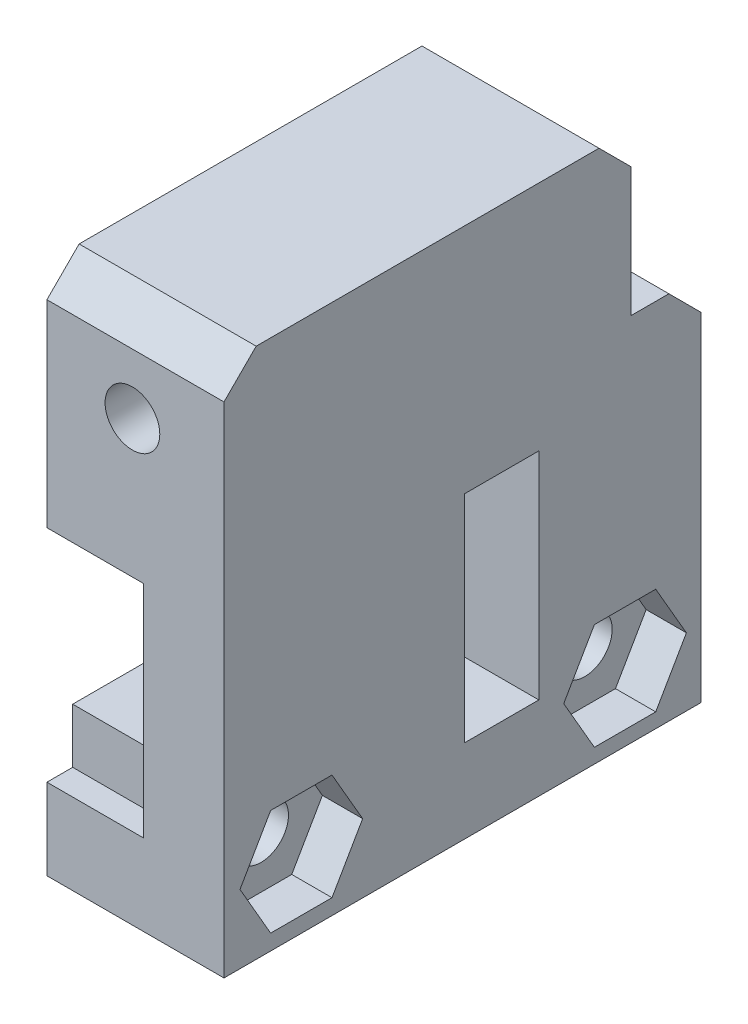
SolidWorks part; units mm, degrees
ref_plane "Front Plane" through (0, 0, 0) normal (0, 0, 1) x (1, 0, 0)
ref_plane "Top Plane" through (0, 0, 0) normal (0, 1, 0) x (1, 0, 0)
ref_plane "Right Plane" through (0, 0, 0) normal (1, 0, 0) x (0, 0, -1)
sketch "Sketch1" plane through (0, 0, 0) normal (1, 0, 0) x (0, 0, -1)
  line L1 (-14.8204, 11.4976) -> (14.8204, 11.4976)
  line L2 (-14.8204, 11.4976) -> (-14.8204, -11.4976)
  line L3 (-14.8204, -11.4976) -> (14.8204, -11.4976)
  line L4 (14.8204, 11.4976) -> (14.8204, -11.4976)
  line L5 (-14.8204, 11.4976) -> (14.8204, -11.4976) construction
  line L6 (-14.8204, -11.4976) -> (14.8204, 11.4976) construction
  point P0 (0, 0)
extrude "Boss-Extrude1" add sketch "Sketch1" along normal blind 11
sketch "Sketch2" plane through (0, 11.4976, 0) normal (0, 1, 0) x (1, 0, 0)
  line L0 (11, 14.8204) -> (11, -14.8204) construction
  line L1 (0, -14.8204) -> (11, -14.8204)
  line L2 (0, -14.8204) -> (0, 10.4797)
  line L3 (0, 10.4797) -> (11, 10.4797)
  line L4 (11, -14.8204) -> (11, 10.4797)
  line L5 (0, -14.8204) -> (11, 10.4797) construction
  line L6 (0, 10.4797) -> (11, -14.8204) construction
  point P0 (5.5, -2.1704)
extrude "Boss-Extrude2" add sketch "Sketch2" along normal blind 10
chamfer "Chamfer1" distance 2 angle 45 3 edges at (5.5, 11.4976, -14.8204) (5.5, 21.4976, -10.4797) (5.5, 21.4976, 14.8204)
sketch "Sketch3" plane through (0, 0, 0) normal (-1, 0, 0) x (0, 0, 1)
  line L1 (-15.4578, 7.2288) -> (15.9867, 7.2288)
  line L2 (-15.4578, 7.2288) -> (-15.4578, -6.4617)
  line L3 (-15.4578, -6.4617) -> (15.9867, -6.4617)
  line L4 (15.9867, 7.2288) -> (15.9867, -6.4617)
  line L5 (-15.4578, 7.2288) -> (15.9867, -6.4617) construction
  line L6 (-15.4578, -6.4617) -> (15.9867, 7.2288) construction
  point P0 (0.2645, 0.3836)
extrude "Cut-Extrude2" cut sketch "Sketch3" against normal blind 6
sketch "Sketch4" plane through (6, 0.4351, 0) normal (-1, 0, 0) x (0, 0, 1)
  line L1 (-10.6052, 3.1028) -> (6.196, 3.1028)
  line L2 (-10.6052, 3.1028) -> (-10.6052, -3.1074)
  line L3 (-10.6052, -3.1074) -> (6.196, -3.1074)
  line L4 (6.196, 3.1028) -> (6.196, -3.1074)
  line L5 (-10.6052, 3.1028) -> (6.196, -3.1074) construction
  line L6 (-10.6052, -3.1074) -> (6.196, 3.1028) construction
  point P0 (-2.2046, -0.0023)
extrude "Boss-Extrude3" add sketch "Sketch4" along normal blind 7
sketch "Sketch5" plane through (0, 0, 6.196) normal (0, 0, 1) x (1, 0, 0)
  circle A0 centre (2.1975, 0.3697) radius 2.041
extrude "Cut-Extrude3" cut sketch "Sketch5" against normal through all contours A0
sketch "Sketch6" plane through (11, 0, 0) normal (1, 0, 0) x (0, 0, -1)
  line L1 (4.7403, 7.0824) -> (0.1188, 7.0824)
  line L2 (4.7403, 7.0824) -> (4.7403, -6.3163)
  line L3 (4.7403, -6.3163) -> (0.1188, -6.3163)
  line L4 (0.1188, 7.0824) -> (0.1188, -6.3163)
  line L5 (4.7403, 7.0824) -> (0.1188, -6.3163) construction
  line L6 (4.7403, -6.3163) -> (0.1188, 7.0824) construction
  point P0 (2.4296, 0.3831)
extrude "Cut-Extrude4" cut sketch "Sketch6" against normal through all contours L4 L3 L2 L1
sketch "Sketch7" plane through (0, 0, 14.8204) normal (0, 0, 1) x (1, 0, 0)
  circle A0 centre (5.3121, 15.7624) radius 1.7
extrude "Cut-Extrude5" cut sketch "Sketch7" against normal blind 27 contours A0
sketch "Sketch15" plane through (11, 0, 0) normal (1, 0, 0) x (0, 0, -1)
  line L1 (-8.1098, -10.532) -> (-6.2046, -7.232)
  line L2 (-6.2046, -7.232) -> (-8.1098, -3.932)
  line L3 (-8.1098, -3.932) -> (-11.9203, -3.932)
  line L4 (-11.9203, -3.932) -> (-13.8256, -7.232)
  line L5 (-13.8256, -7.232) -> (-11.9203, -10.532)
  line L6 (-11.9203, -10.532) -> (-8.1098, -10.532)
  circle A0 centre (-10.0151, -7.232) radius 3.3 construction
sketch "Sketch17" plane through (11, 0, 0) normal (1, 0, 0) x (0, 0, -1)
  line L1 (12.0026, -10.5904) -> (13.9079, -7.2904)
  line L2 (13.9079, -7.2904) -> (12.0026, -3.9904)
  line L3 (12.0026, -3.9904) -> (8.1921, -3.9904)
  line L4 (8.1921, -3.9904) -> (6.2869, -7.2904)
  line L5 (6.2869, -7.2904) -> (8.1921, -10.5904)
  line L6 (8.1921, -10.5904) -> (12.0026, -10.5904)
  circle A0 centre (10.0974, -7.2904) radius 3.3 construction
sketch "Sketch18" plane through (11, 0, 0) normal (1, 0, 0) x (0, 0, -1)
  circle A0 centre (10.0974, -7.2904) radius 1.7
sketch "Sketch19" plane through (11, 0, 0) normal (1, 0, 0) x (0, 0, -1)
  circle A0 centre (-10.0151, -7.232) radius 1.7
sketch "Sketch20" plane through (11, 0, 0) normal (1, 0, 0) x (0, 0, -1)
  line L1 (-13.2201, -3.0643) -> (-6.81, -3.0643)
  line L2 (-13.2201, -3.0643) -> (-13.2201, -11.3998)
  line L3 (-13.2201, -11.3998) -> (-6.81, -11.3998)
  line L4 (-6.81, -3.0643) -> (-6.81, -11.3998)
  line L5 (-13.2201, -3.0643) -> (-6.81, -11.3998) construction
  line L6 (-13.2201, -11.3998) -> (-6.81, -3.0643) construction
  point P0 (-10.0151, -7.232)
sketch "Sketch21" plane through (11, 0, 0) normal (1, 0, 0) x (0, 0, -1)
  line L1 (6.8923, -3.1226) -> (13.3024, -3.1226)
  line L2 (6.8923, -3.1226) -> (6.8923, -11.4581)
  line L3 (6.8923, -11.4581) -> (13.3024, -11.4581)
  line L4 (13.3024, -3.1226) -> (13.3024, -11.4581)
  line L5 (6.8923, -3.1226) -> (13.3024, -11.4581) construction
  line L6 (6.8923, -11.4581) -> (13.3024, -3.1226) construction
  point P0 (10.0974, -7.2904)
extrude "Boss-Extrude4" add sketch "Sketch21" against normal blind 11
extrude "Boss-Extrude5" add sketch "Sketch20" against normal blind 11
extrude "Cut-Extrude6" cut sketch "Sketch15" against normal blind 2.5
extrude "Cut-Extrude7" cut sketch "Sketch19" against normal through all
extrude "Cut-Extrude8" cut sketch "Sketch17" against normal blind 2.5
extrude "Cut-Extrude9" cut sketch "Sketch18" against normal through all
